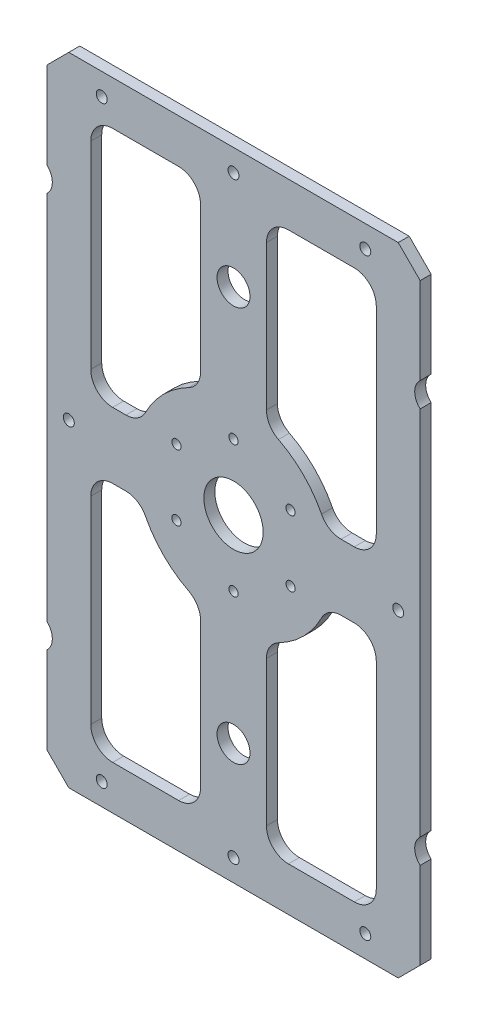
SolidWorks part; units mm, degrees
ref_plane "正面" through (0, 0, 0) normal (0, 0, 1) x (1, 0, 0)
ref_plane "平面" through (0, 0, 0) normal (0, 1, 0) x (1, 0, 0)
ref_plane "右側面" through (0, 0, 0) normal (1, 0, 0) x (0, 0, -1)
sketch "ｽｹｯﾁ1" plane through (0, 0, 0) normal (0, 0, 1) x (1, 0, 0)
  line L1 (-85, 145) -> (85, 145)
  line L2 (-85, 145) -> (-85, -145)
  line L3 (-85, -145) -> (85, -145)
  line L4 (85, 145) -> (85, -145)
  line L5 (-85, 145) -> (85, -145) construction
  line L6 (-85, -145) -> (85, 145) construction
  point P0 (0, 0)
  dimension "D1" = 170
  dimension "D2" = 290
extrude "ﾎﾞｽ - 押し出し1" add sketch "ｽｹｯﾁ1" along normal blind 5
sketch "ｽｹｯﾁ2" plane through (0, 0, 5) normal (0, 0, 1) x (1, 0, 0)
  circle A0 centre (0, 0) radius 13.5
  dimension "D1" = 27
extrude "ｶｯﾄ - 押し出し1" cut sketch "ｽｹｯﾁ2" against normal through all
sketch "ｽｹｯﾁ3" plane through (0, 0, 5) normal (0, 0, 1) x (1, 0, 0)
  line L0 (85, -145) -> (85, 145) construction
  line L1 (-75, 135) -> (75, 135) construction
  line L2 (-75, 135) -> (-75, -135) construction
  line L3 (-75, -135) -> (75, -135) construction
  line L4 (75, 135) -> (75, -135) construction
  line L5 (-75, 135) -> (75, -135) construction
  line L6 (-75, -135) -> (75, 135) construction
  line L7 (85, 145) -> (-85, 145) construction
  line L8 (-85, 0) -> (85, 0) construction
  line L9 (-85, 145) -> (-85, -145) construction
  line L10 (0, 145) -> (0, -145) construction
  line L11 (-85, -145) -> (85, -145) construction
  line L12 (-60, 135) -> (-60, -135) construction
  line L13 (60, 135) -> (60, -135) construction
  circle A0 centre (-75, 0) radius 2.5
  circle A1 centre (0, 135) radius 2.5
  circle A2 centre (75, 0) radius 2.5
  circle A3 centre (0, -135) radius 2.5
  circle A4 centre (-60, 135) radius 2.5
  circle A5 centre (60, 135) radius 2.5
  circle A6 centre (60, -135) radius 2.5
  circle A7 centre (-60, -135) radius 2.5
  point P0 (0, 0)
  dimension "D3" = 5
  dimension "D1" = 10
  dimension "D2" = 10
  dimension "D4" = 60
extrude "ｶｯﾄ - 押し出し2" cut sketch "ｽｹｯﾁ3" against normal through all
chamfer "面取り1" distance 10 angle 45 4 edges at (85, -145, 2.5) (-85, -145, 2.5) (-85, 145, 2.5) (85, 145, 2.5)
sketch "ｽｹｯﾁ4" plane through (0, 0, 5) normal (0, 0, 1) x (1, 0, 0)
  line L0 (0, 0) -> (0, 90) construction
  line L1 (0, 90) -> (90, 90) construction
  line L2 (-75, 0) -> (75, 0) construction
  line L3 (0, 0) -> (0, -30) construction
  line L4 (0, 0) -> (-25.9808, 15) construction
  line L5 (0, 0) -> (25.9808, 15) construction
  circle A0 centre (90, 90) radius 7.5
  circle A1 centre (0, 90) radius 7.5
  circle A2 centre (-90, 90) radius 7.5
  circle A4 centre (-90, -90) radius 7.5
  circle A5 centre (0, -90) radius 7.5
  circle A6 centre (90, -90) radius 7.5
  circle A8 centre (0, -30) radius 2.1
  circle A9 centre (-25.9808, -15) radius 2.1
  circle A10 centre (-25.9808, 15) radius 2.1
  circle A11 centre (0, 30) radius 2.1
  circle A12 centre (25.9808, 15) radius 2.1
  circle A13 centre (25.9808, -15) radius 2.1
  dimension "D1" = 90
  dimension "D3" = 15
  dimension "D4" = 6
  dimension "D6" = 4.2
  dimension "D2" = 90
  dimension "D5" = 30
extrude "ｶｯﾄ - 押し出し3" cut sketch "ｽｹｯﾁ4" against normal through all
sketch "ｽｹｯﾁ5" plane through (0, 0, 5) normal (0, 0, 1) x (1, 0, 0)
  line L0 (-65, 125) -> (-65, 15)
  line L1 (-65, 15) -> (-42.4264, 15)
  line L4 (-15, 42.4264) -> (-15, 125)
  line L5 (-15, 125) -> (-65, 125)
  line L6 (-85, 84.4098) -> (-85, -84.4098) construction
  line L7 (75, 145) -> (-75, 145) construction
  line L8 (0, 145) -> (0, 0) construction
  line L9 (0, 0) -> (-85, 0) construction
  line L10 (15, 42.4264) -> (15, 125)
  line L11 (15, 125) -> (65, 125)
  line L12 (65, 125) -> (65, 15)
  line L13 (65, 15) -> (42.4264, 15)
  line L14 (-15, -42.4264) -> (-15, -125)
  line L15 (-15, -125) -> (-65, -125)
  line L16 (-65, -125) -> (-65, -15)
  line L17 (-65, -15) -> (-42.4264, -15)
  line L18 (15, -42.4264) -> (15, -125)
  line L19 (15, -125) -> (65, -125)
  line L20 (65, -125) -> (65, -15)
  line L21 (65, -15) -> (42.4264, -15)
  arc A0 (-15, 42.4264) -> (-42.4264, 15) centre (0, 0) ccw
  arc A1 (15, 42.4264) -> (42.4264, 15) centre (0, 0) cw
  arc A2 (-15, -42.4264) -> (-42.4264, -15) centre (0, 0) cw
  arc A3 (15, -42.4264) -> (42.4264, -15) centre (0, 0) ccw
  dimension "D1" = 45
  dimension "D2" = 20
  dimension "D3" = 20
  dimension "D4" = 15
  dimension "D5" = 15
extrude "ｶｯﾄ - 押し出し4" cut sketch "ｽｹｯﾁ5" against normal through all
fillet "ﾌｨﾚｯﾄ1" radius 10 20 edges at (-65, -15, 2.5) (-15, -125, 2.5) (-65, -125, 2.5) (-15, -42.4264, 2.5) (-42.4264, -15, 2.5) (15, -125, 2.5) (15, -42.4264, 2.5) (42.4264, -15, 2.5) (65, -15, 2.5) (65, -125, 2.5) (65, 15, 2.5) (65, 125, 2.5) (15, 125, 2.5) (42.4264, 15, 2.5) (15, 42.4264, 2.5) (-15, 42.4264, 2.5) (-42.4264, 15, 2.5) (-65, 15, 2.5) (-15, 125, 2.5) (-65, 125, 2.5)
